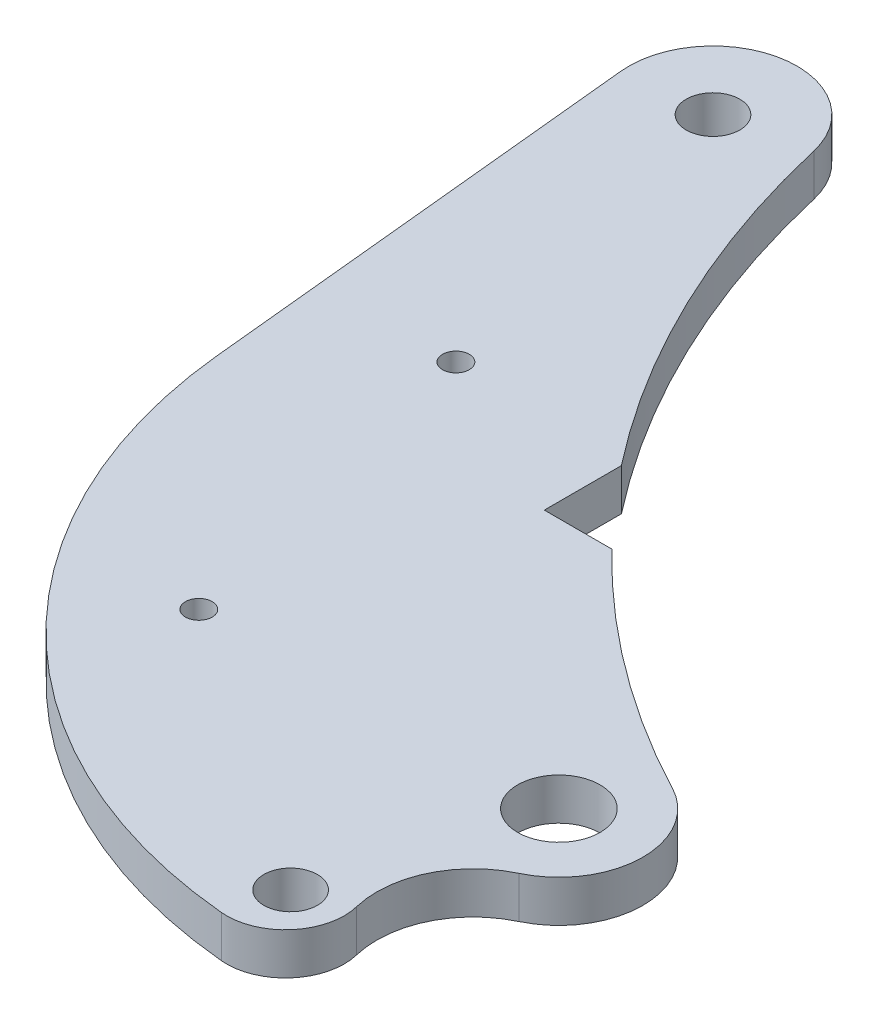
SolidWorks part; units mm, degrees
ref_plane "Front" through (0, 0, 0) normal (0, 0, 1) x (1, 0, 0)
ref_plane "Top" through (0, 0, 0) normal (0, 1, 0) x (1, 0, 0)
ref_plane "Right" through (0, 0, 0) normal (1, 0, 0) x (0, 0, -1)
ref_axis "side-side" through (80.9, 0, 0) along (-1, 0, 0)
ref_axis "up-down" through (0, 50, 0) along (0, -1, 0)
ref_axis "front-back" through (0, 0, -80.9) along (0, 0, 1)
sketch "Sketch1" plane through (0, 0, 0) normal (0, 1, 0) x (1, 0, 0)
  line L0 (30.607, -49.5919) -> (30.607, -72.1164) construction
  line L1 (54.5672, -104.6448) -> (42.2759, -98.926) construction
  line L2 (0, -50) -> (0, 50) construction
  line L3 (-9.9207, -0.9853) -> (-4.6453, -54.1028)
  line L4 (30.607, -41.4649) -> (30.607, -50.6079)
  line L5 (30.607, -50.6079) -> (38.6058, -50.6079)
  line L7 (35.56, -49.5919) -> (30.607, -49.5919) construction
  circle A0 centre (0, 0) radius 3.175
  circle A1 centre (62.123, -80.3946) radius 4.8895
  circle A2 centre (54.5672, -104.6448) radius 3.175
  arc A3 (9.7129, 2.2475) -> (30.607, -41.4649) centre (118.5958, 27.4428) ccw
  arc A4 (66.399, -89.4005) -> (66.7481, -71.5628) centre (62.123, -80.3946) ccw
  arc A5 (52.782, -111.0652) -> (60.2, -102.4464) centre (53.4158, -104.109) ccw
  arc A6 (60.2, -102.4464) -> (66.399, -89.4005) centre (71.3015, -99.7258) cw
  arc A7 (9.7129, 2.2475) -> (-9.9207, -0.9853) centre (0, 0) ccw
  arc A8 (52.782, -111.0652) -> (-4.6453, -54.1028) centre (58.5438, -47.8271) cw
  circle A9 centre (10.16, -40.64) radius 1.5875 construction
  circle A10 centre (20.32, -81.28) radius 1.5875 construction
  circle A11 centre (10.16, -40.64) radius 1.5875
  circle A12 centre (20.32, -81.28) radius 1.5875
  arc A13 (38.6058, -50.6079) -> (66.7481, -71.5628) centre (118.5958, 27.4428) ccw
  dimension "D1" = 6.35
  dimension "D2" = 2.54
  dimension "D3" = 19.939
  dimension "D4" = 13.97
  dimension "D6" = 11.43
  dimension "D7" = 111.76
  dimension "D9" = 63.5
  dimension "D11" = 9.779
  dimension "D12" = 5.08
  dimension "D5" = 65.049
  dimension "D8" = 5.672
  dimension "D10" = 1.016
extrude "Boss-Extrude1" add sketch "Sketch1" along normal mid plane 4.953
